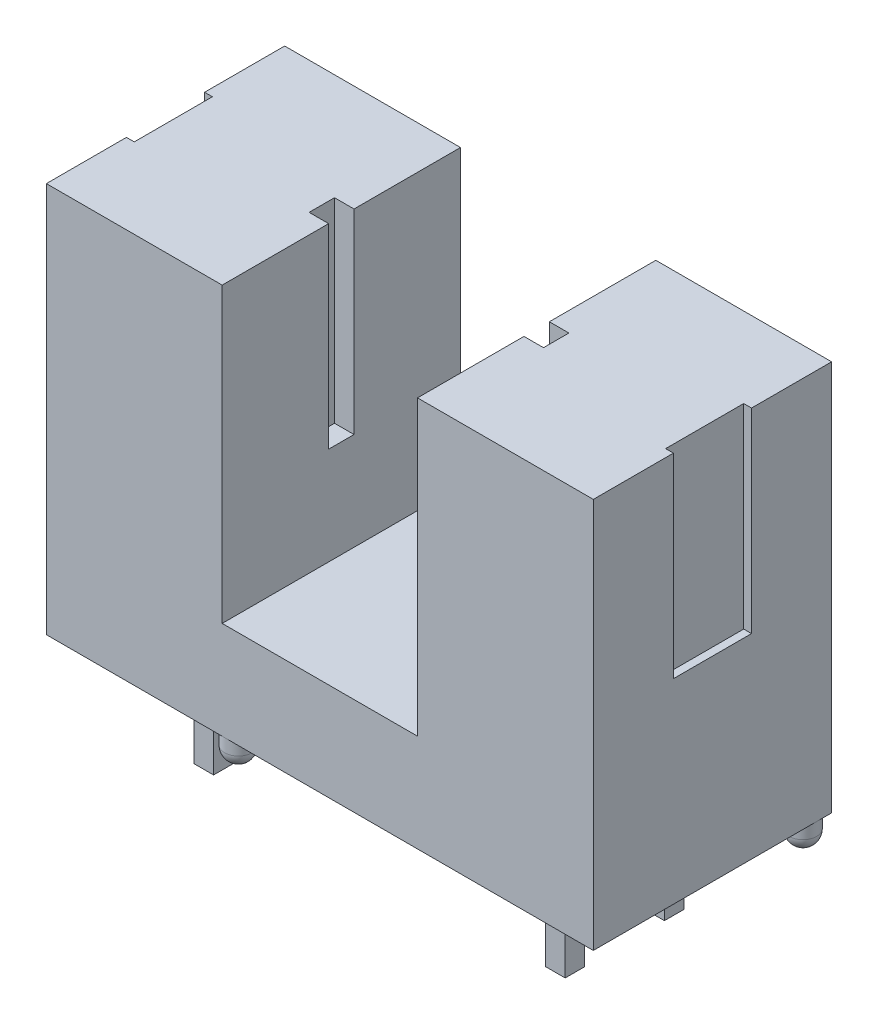
SolidWorks part; units mm, degrees
ref_plane "Front Plane" through (0, 0, 0) normal (0, 0, 1) x (1, 0, 0)
ref_plane "Top Plane" through (0, 0, 0) normal (0, 1, 0) x (1, 0, 0)
ref_plane "Right Plane" through (0, 0, 0) normal (1, 0, 0) x (0, 0, -1)
sketch "Sketch1" plane through (0, 0, 0) normal (0, 0, 1) x (1, 0, 0)
  line L0 (2.5, 10) -> (7, 10)
  line L1 (-7, 10) -> (-2.5, 10)
  line L2 (-7, 10) -> (-7, 0)
  line L3 (-7, 0) -> (7, 0)
  line L4 (7, 10) -> (7, 0)
  line L6 (-2.5, 10) -> (-2.5, 2.5)
  line L7 (-2.5, 2.5) -> (2.5, 2.5)
  line L8 (2.5, 10) -> (2.5, 2.5)
  dimension "D1" = 5
  dimension "D2" = 2.5
  dimension "D3" = 2.5
  dimension "D4" = 10
  dimension "D5" = 14
  dimension "D6" = 7
extrude "Extrude1" add sketch "Sketch1" along normal blind 3.05 and the other way blind 3.05
ref_plane "Plane1" through (-4.5, 0, 0) normal (1, 0, 0) x (0, 0, -1)
ref_plane "Plane2" through (4.5, 0, 0) normal (1, 0, 0) x (0, 0, -1)
sketch "Sketch2" plane through (4.5, 0, 0) normal (1, 0, 0) x (0, 0, -1)
  line L0 (1.27, 0) -> (1.27, -2.5)
  line L1 (-3.05, 0) -> (3.05, 0) construction
  line L2 (-1.27, 0) -> (-1.27, -2.5)
  dimension "D1" = 2.54
  dimension "D2" = 1.27
  dimension "D3" = 2.5
extrude "Extrude-Thin1" add sketch "Sketch2" along normal blind 0.25 and the other way blind 0.25 thin contours L0 thin type mid plane wall 0.5
extrude "Extrude-Thin2" add sketch "Sketch2<3>" along normal blind 0.25 and the other way blind 0.25 thin contours L2 thin type mid plane wall 0.5
sketch "Sketch2<3>" plane through (4.5, 0, 0) normal (1, 0, 0) x (0, 0, -1) same geometry as "Sketch2"
sketch "Sketch3" plane through (-4.5, 0, 0) normal (1, 0, 0) x (0, 0, -1)
  line L0 (-1.27, 0) -> (-1.27, -2.5) construction
  line L1 (1.27, 0) -> (1.27, -2.5) construction
  line L2 (-1.27, 0) -> (-1.27, -2.5)
  line L3 (1.27, 0) -> (1.27, -2.5)
extrude "Extrude-Thin3" add sketch "Sketch3" along normal blind 0.25 and the other way blind 0.25 thin contours L3 thin type mid plane wall 0.5
extrude "Extrude-Thin4" add sketch "Sketch3<3>" along normal blind 0.25 and the other way blind 0.25 thin contours L2 thin type mid plane wall 0.5
sketch "Sketch3<3>" plane through (-4.5, 0, 0) normal (1, 0, 0) x (0, 0, -1) same geometry as "Sketch3"
sketch "Sketch4" plane through (0, 0, 0) normal (0, 1, 0) x (1, 0, 0)
  line L0 (-7, -3.05) -> (-7, 3.05) construction
  circle A0 centre (-2.45, -2.6858) radius 0.35
  circle A1 centre (6.6306, 2.687) radius 0.35
  dimension "D1" = 4.55
extrude "Extrude2" add sketch "Sketch4" against normal blind 0.7
fillet "Fillet1" radius 0.35 2 edges at (6.6306, -0.7, -2.337) (-2.45, -0.7, 3.0358)
sketch "Sketch5" plane through (7, 0, 0) normal (1, 0, 0) x (0, 0, -1)
  line L0 (-3.05, 10) -> (3.05, 10) construction
  line L1 (-1, 10) -> (1, 10)
  line L2 (-1, 10) -> (-1, 5)
  line L3 (-1, 5) -> (1, 5)
  line L4 (1, 10) -> (1, 5)
extrude "Cut-Extrude1" cut sketch "Sketch5" against normal blind 0.2
sketch "Sketch6" plane through (-7, 0, 0) normal (-1, 0, 0) x (0, 0, 1)
  line L4 (1, 10) -> (-1, 10)
  line L5 (-1, 10) -> (-1, 5)
  line L6 (-1, 5) -> (1, 5)
  line L7 (1, 5) -> (1, 10)
  line L8 (1, 10) -> (-1, 10)
  line L9 (-1, 10) -> (-1, 5)
  line L10 (-1, 5) -> (1, 5)
  line L11 (1, 5) -> (1, 10)
  dimension "D1" = 0
extrude "Cut-Extrude2" cut sketch "Sketch6" against normal blind 0.2
sketch "Sketch7" plane through (2.5, 0, 0) normal (-1, 0, 0) x (0, 0, 1)
  line L8 (0.325, 10.0454) -> (-0.325, 10.0454)
  line L9 (-0.325, 10.0454) -> (-0.325, 5)
  line L10 (-0.325, 5) -> (0.325, 5)
  line L11 (0.325, 5) -> (0.325, 10.0454)
extrude "Cut-Extrude3" cut sketch "Sketch7" against normal blind 0.5
sketch "Sketch8" plane through (-2.5, 0, 0) normal (1, 0, 0) x (0, 0, -1)
  line L4 (0.325, 10.0454) -> (-0.325, 10.0454)
  line L5 (0.325, 5) -> (0.325, 10.0454)
  line L6 (-0.325, 5) -> (0.325, 5)
  line L7 (-0.325, 10.0454) -> (-0.325, 5)
  line L8 (0.325, 10.0454) -> (-0.325, 10.0454)
  line L9 (0.325, 5) -> (0.325, 10.0454)
  line L10 (-0.325, 5) -> (0.325, 5)
  line L11 (-0.325, 10.0454) -> (-0.325, 5)
  dimension "D1" = 0
extrude "Cut-Extrude4" cut sketch "Sketch8" against normal blind 0.5
ref_plane "Board Plane" through (0, -0.7, 0) normal (0, 1, 0) x (-1, 0, 0)
sketch "Component_Outline" plane through (0, -0.7, 0) normal (0, 1, 0) x (-1, 0, 0)
  line L1 (-7, -3.05) -> (7, -3.05)
  line L2 (-7, -3.05) -> (-7, 3.05)
  line L3 (-7, 3.05) -> (7, 3.05)
  line L4 (7, -3.05) -> (7, 3.05)
  point P6 (0, 0)
